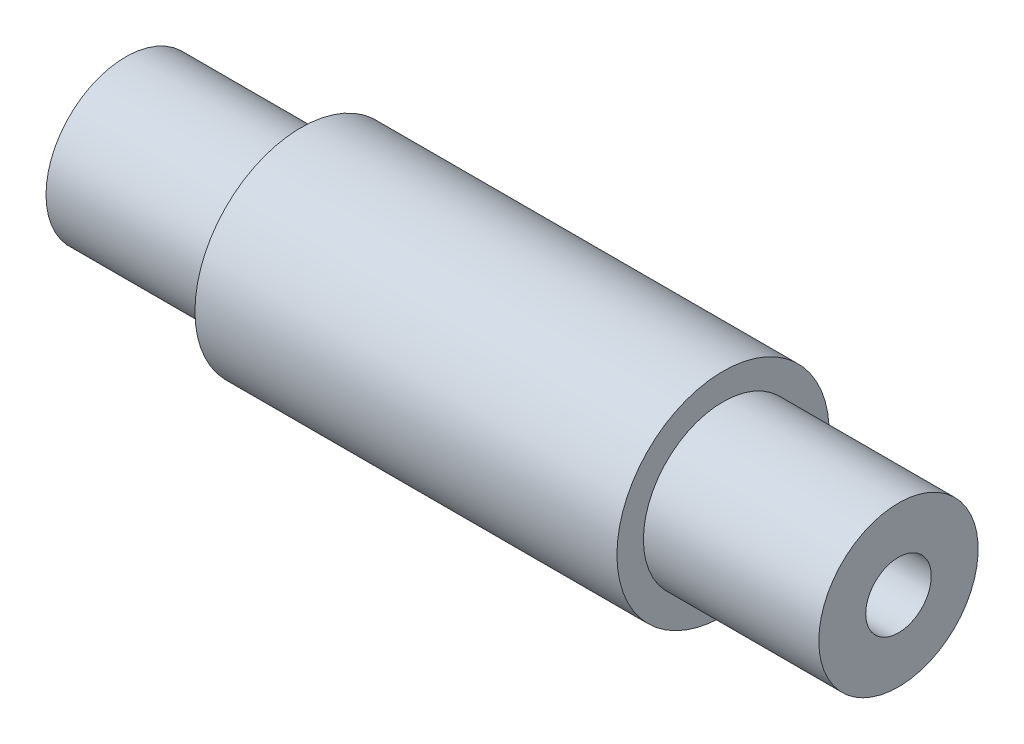
SolidWorks part; units mm, degrees
ref_plane "Front Plane" through (0, 0, 0) normal (0, 0, 1) x (1, 0, 0)
ref_plane "Top Plane" through (0, 0, 0) normal (0, 1, 0) x (1, 0, 0)
ref_plane "Right Plane" through (0, 0, 0) normal (1, 0, 0) x (0, 0, -1)
sketch "Filter_F2 Sketch" plane through (0, 0, 0) normal (0, 0, 1) x (1, 0, 0)
  line L0 (-1000, 0) -> (1000, 0) construction
  line L1 (-37.45, 0) -> (-37.45, 7.722)
  line L2 (-37.45, 7.722) -> (-20.45, 7.722)
  line L3 (-20.45, 7.722) -> (-20.45, 10.287)
  line L4 (-20.45, 10.287) -> (20.45, 10.287)
  line L5 (20.45, 10.287) -> (20.45, 7.722)
  line L6 (20.45, 7.722) -> (37.45, 7.722)
  line L7 (37.45, 7.722) -> (37.45, 0)
  line L8 (37.45, 0) -> (-37.45, 0)
revolve "Filter_F2" add sketch "Filter_F2 Sketch" angle 360 about L0
ref_axis "Engine Axis" through (41.195, 0, 0) along (-1, 0, 0)
sketch "Socket 1 Sketch" plane through (0, 0, 0) normal (0, 0, 1) x (1, 0, 0)
  line L0 (-1000, 0) -> (1000, 0) construction
  line L1 (-38.45, 0) -> (-38.45, 3.175)
  line L2 (-38.45, 3.175) -> (-22.25, 3.175)
  line L3 (-22.25, 3.175) -> (-22.25, 0)
  line L4 (-22.25, 0) -> (-38.45, 0)
revolve "Socket 1" cut sketch "Socket 1 Sketch" angle 360 about L0
sketch "Socket 2 Sketch" plane through (0, 0, 0) normal (0, 0, 1) x (1, 0, 0)
  line L0 (-1000, 0) -> (1000, 0) construction
  line L1 (22.25, 0) -> (22.25, 3.175)
  line L2 (22.25, 3.175) -> (38.45, 3.175)
  line L3 (38.45, 3.175) -> (38.45, 0)
  line L4 (38.45, 0) -> (22.25, 0)
revolve "Socket 2" cut sketch "Socket 2 Sketch" angle 360 about L0
